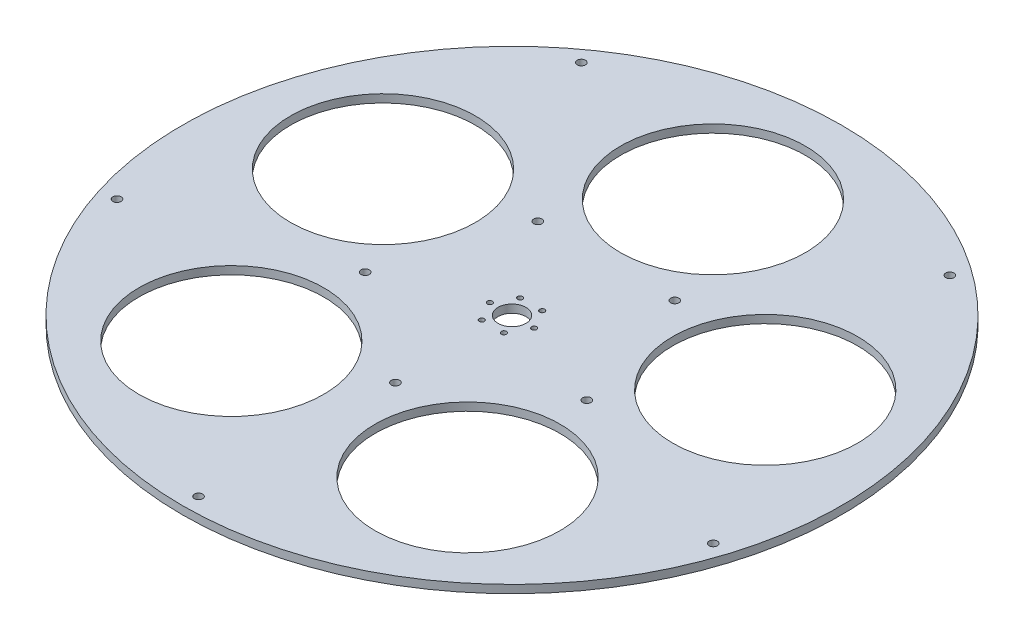
SolidWorks part; units mm, degrees
material "PC High Viscosity"
ref_plane "Front Plane" through (0, 0, 0) normal (0, 0, 1) x (1, 0, 0)
ref_plane "Top Plane" through (0, 0, 0) normal (0, 1, 0) x (1, 0, 0)
ref_plane "Right Plane" through (0, 0, 0) normal (1, 0, 0) x (0, 0, -1)
sketch "Sketch1" plane through (0, 0, 0) normal (0, 1, 0) x (1, 0, 0)
  circle A0 centre (0, 0) radius 260.35
  circle A1 centre (0, 158.75) radius 73.025
  circle A2 centre (150.9802, 49.0564) radius 73.025
  circle A3 centre (93.3109, -128.4314) radius 73.025
  circle A4 centre (-93.3109, -128.4314) radius 73.025
  circle A5 centre (-150.9802, 49.0564) radius 73.025
  point P15 (0, 0)
  dimension "D1" = 520.7
  dimension "D2" = 146.05
  dimension "D3" = 158.75
  dimension "D4" = 5
extrude "Boss-Extrude1" add sketch "Sketch1" along normal blind 6.35
sketch "Sketch3" plane through (-5.1845, 6.35, -2.4486) normal (0, 1, 0) x (1, 0, 0)
  circle A0 centre (5.1845, -2.4486) radius 11
  circle A1 centre (5.1845, -2.4486) radius 260.35 construction
  dimension "D1" = 22
extrude "Cut-Extrude1" cut sketch "Sketch3" against normal through all
hole_wizard "#10-32 Tapped Hole1" positions "Sketch5" profile "Sketch7" tap size "#10-32" standard "ANSI Inch" end condition through all
sketch "Sketch5" plane through (-5.1845, 6.35, -2.4486) normal (0, 1, 0) x (1, 0, 0)
  line L0 (5.1845, -2.4486) -> (-3.5467, 12.6744) construction
  line L2 (5.1845, -2.4486) -> (5.1845, 15.0139) construction
  circle A0 centre (5.1845, -2.4486) radius 17.4625
  point P0 (-3.5467, 12.6744)
  point P22 (13.9158, 12.6744)
  point P23 (22.647, -2.4486)
  point P24 (13.9158, -17.5715)
  point P25 (-3.5467, -17.5715)
  point P26 (-12.278, -2.4486)
  dimension "D1" = 34.925
  dimension "D2" = 30
  dimension "D3" = 6
sketch "Sketch7" plane through (-8.7313, 6.35, -15.123) normal (1, 0, 0) x (0, 0, 1)
  line L0 (0, 0) -> (0, 6.35)
  line L1 (0, 6.35) -> (2.0193, 6.35)
  line L2 (2.0193, 6.35) -> (2.0193, 0)
  line L5 (2.0193, 0) -> (0, 0)
  line L11 (0, -6.35) -> (0, 107.95) construction
  dimension "Thru Tap Drill Dia." = 4.0386
  dimension "Thru Tap Drill Depth" = 6.35
cosmetic thread "Hole Thread1" parameters "D2"=4.826
cosmetic thread "Hole Thread2" parameters "D2"=4.826
cosmetic thread "Hole Thread3" parameters "D2"=4.826
cosmetic thread "Hole Thread4" parameters "D2"=4.826
cosmetic thread "Hole Thread5" parameters "D2"=4.826
cosmetic thread "Hole Thread6" parameters "D2"=4.826
sketch "Sketch8" plane through (0, 6.35, 0) normal (0, 1, 0) x (1, 0, 0)
  circle A0 centre (0, -247.65) radius 3.2512
  circle A1 centre (-235.5291, -76.5281) radius 3.2512
  circle A2 centre (-145.565, 200.3531) radius 3.2512
  circle A3 centre (145.565, 200.3531) radius 3.2512
  circle A4 centre (235.5291, -76.5281) radius 3.2512
  point P14 (0, 0)
  dimension "D2" = 6.5024
  dimension "D1" = 247.65
  dimension "D3" = 5
extrude "Cut-Extrude2" cut sketch "Sketch8" against normal through all
sketch "Sketch9" plane through (0, 6.35, 0) normal (0, 1, 0) x (1, 0, 0)
  line L0 (0, -92.075) -> (0, 0)
  circle A0 centre (0, 0) radius 92.075 construction
  circle A1 centre (0, -92.075) radius 3.2639
  dimension "D1" = 184.15
  dimension "D2" = 6.5278
extrude "Cut-Extrude3" cut sketch "Sketch9" against normal through all contours A1
pattern_circular "CirPattern1" count 5 over 360 about axis through (0, 6.35, 0) along (0, 1, 0) of "Cut-Extrude3"
